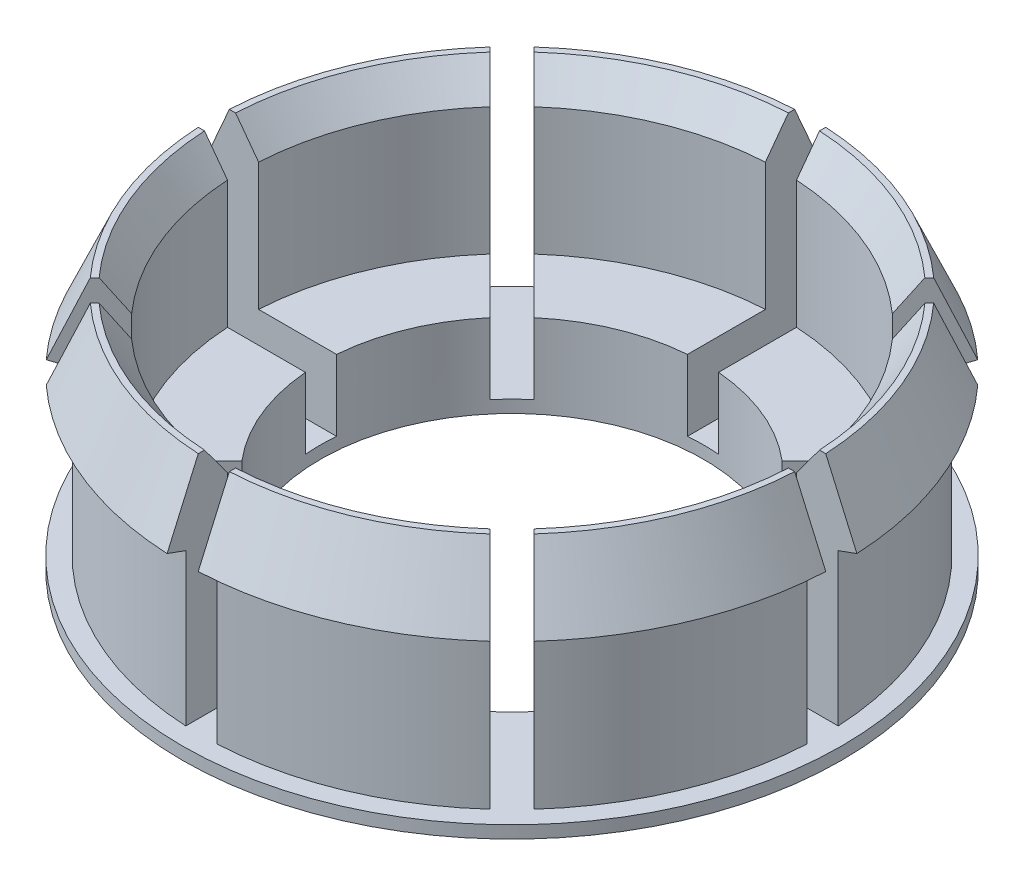
SolidWorks part; units mm, degrees
ref_plane "Front Plane" through (0, 0, 0) normal (0, 0, 1) x (1, 0, 0)
ref_plane "Top Plane" through (0, 0, 0) normal (0, 1, 0) x (1, 0, 0)
ref_plane "Right Plane" through (0, 0, 0) normal (1, 0, 0) x (0, 0, -1)
sketch "Sketch5" plane through (0, 0, 0) normal (0, 0, 1) x (1, 0, 0)
  line L0 (-11, -3.2385) -> (-11, 1.9685)
  line L1 (11, 3.2385) -> (-11, 3.2385) construction
  line L2 (11, 3.2385) -> (11, -3.2385) construction
  line L3 (11, -3.2385) -> (-11, -3.2385) construction
  line L4 (-11, 1.9685) -> (-11, -3.2385) construction
  line L5 (11, 3.2385) -> (-11, -3.2385) construction
  line L6 (11, -3.2385) -> (-11, 3.2385) construction
  line L7 (-11.938, 3.2385) -> (-12.192, 3.2385)
  line L8 (-12.192, 3.2385) -> (-13.462, 0.3408)
  line L9 (-13.462, 0.3408) -> (-12.7, 0.0635)
  line L10 (-12.7, 0.0635) -> (-12.7, -6.1365)
  line L11 (-12.7, -6.1365) -> (-13.462, -6.1365)
  line L12 (-13.462, -6.1365) -> (-13.462, -6.6445)
  line L13 (-13.462, -6.6445) -> (-7.825, -6.6445)
  line L14 (-7.825, -6.6445) -> (-7.825, -3.2385)
  line L15 (-7.825, -3.2385) -> (-11, -3.2385)
  line L16 (0, 0.0635) -> (0, -8.827) construction
  line L17 (7.825, -6.6445) -> (-7.825, -6.6445) construction
  line L18 (7.825, -6.6445) -> (7.825, -3.2385) construction
  line L19 (7.825, -3.2385) -> (-7.825, -3.2385) construction
  line L20 (-7.825, -6.6445) -> (-7.825, -3.2385) construction
  line L21 (7.825, -6.6445) -> (-7.825, -3.2385) construction
  line L22 (7.825, -3.2385) -> (-7.825, -6.6445) construction
  line L23 (12.7, -6.1365) -> (-12.7, -6.1365) construction
  line L24 (12.7, -6.1365) -> (12.7, 0.0635) construction
  line L25 (12.7, 0.0635) -> (-12.7, 0.0635) construction
  line L26 (-12.7, -6.1365) -> (-12.7, 0.0635) construction
  line L27 (12.7, -6.1365) -> (-12.7, 0.0635) construction
  line L28 (12.7, 0.0635) -> (-12.7, -6.1365) construction
  line L29 (-11.938, 3.2385) -> (-11, 1.9685)
  line L30 (11, 3.7615) -> (-11, 3.7615) construction
  line L31 (11, 3.7615) -> (11, -3.2385) construction
  line L32 (11, -3.2385) -> (-11, -3.2385) construction
  line L33 (-11, 3.7615) -> (-11, 3.2385) construction
  line L34 (11, 3.7615) -> (-11, -3.2385) construction
  line L35 (11, -3.2385) -> (-11, 3.7615) construction
  line L36 (-11, 1.9685) -> (-11, 3.2385) construction
  line L37 (-11, 3.2385) -> (-11, 1.9685) construction
  line L38 (-11, 3.2385) -> (-11, 1.9685) construction
  line L39 (-11, 1.9685) -> (-11, -3.2385) construction
  line L40 (-11, 3.2385) -> (-11.938, 3.2385) construction
  point P0 (0, 0)
  point P7 (0, -4.9415)
  point P15 (0, 0.2615)
  point P19 (0, -3.0365)
  point P30 (0, 0)
  dimension "D2" = 22
  dimension "D4" = 6.2
  dimension "D6" = 25.4
  dimension "D7" = 0.762
  dimension "D8" = 1.27
  dimension "D9" = 0.508
  dimension "D3" = 3.175
  dimension "D10" = 0.762
  dimension "D5" = 3.175
  dimension "D11" = 70
  dimension "D12" = 3.302
  dimension "D13" = 7
  dimension "D14" = 1.27
  dimension "D15" = 0.254
revolve "Revolve1" add sketch "Sketch5" angle 360 about L16
sketch "Sketch6" plane through (0, 3.2385, 0) normal (0, 1, 0) x (1, 0, 0)
  line L1 (0.635, 0) -> (-0.635, 0)
  line L2 (0.635, 0) -> (0.635, 13.462)
  line L3 (0.635, 13.462) -> (-0.635, 13.462)
  line L4 (-0.635, 0) -> (-0.635, 13.462)
  line L5 (0.635, 0) -> (-0.635, 13.462) construction
  line L6 (0.635, 13.462) -> (-0.635, 0) construction
  circle A0 centre (0, 0) radius 13.462 construction
  point P0 (0, 6.731)
  dimension "D1" = 1.27
extrude "Cut-Extrude3" cut sketch "Sketch6" against normal up to surface (9.375 mm away) and the other way through all up to face at (0, -6.1365, 13.462)
ref_axis "Axis1" through (0, 4.0728, 0) along (0, -1, 0)
pattern_circular "CirPattern1" count 8 over 360 about axis through (0, 4.0728, 0) along (0, -1, 0) of "Cut-Extrude3"
equation "\"D4@Sketch5\"=6.2mm"
